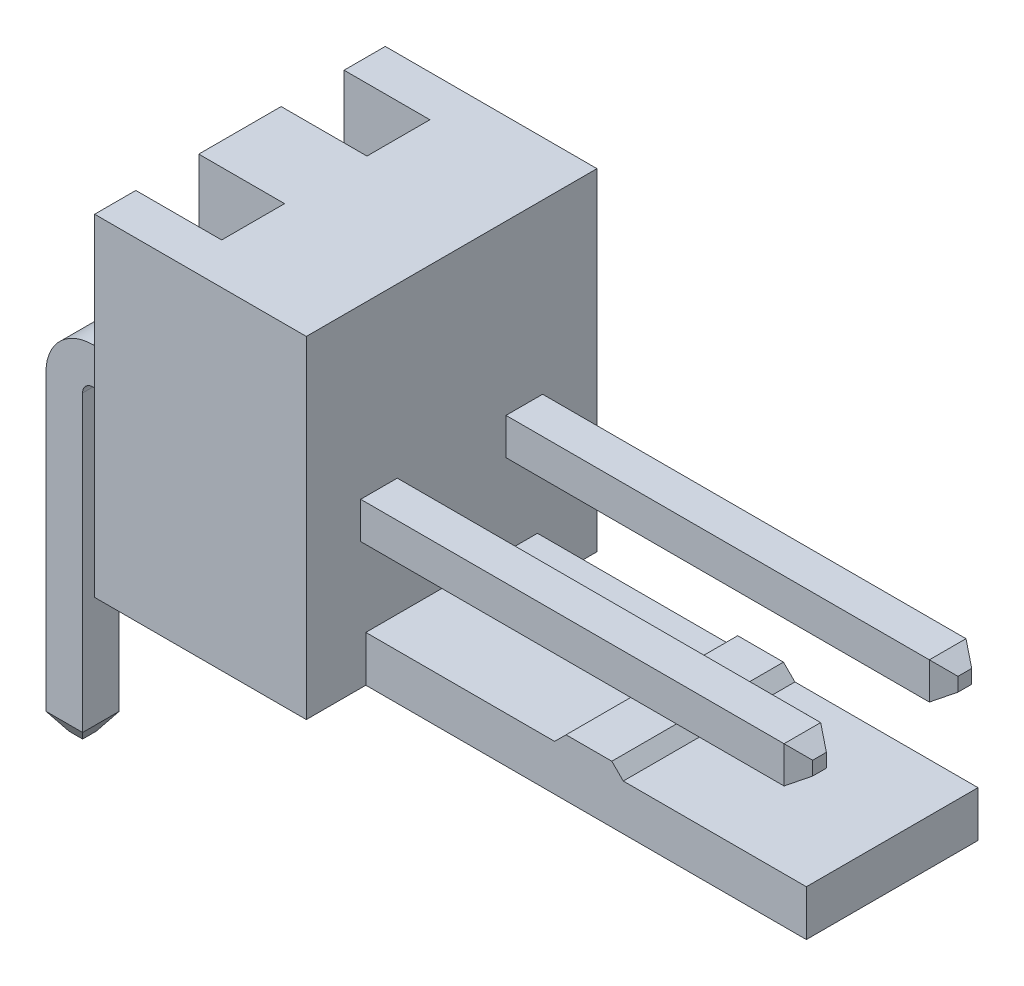
SolidWorks part; units mm, degrees
ref_plane "Спереди" through (0, 0, 0) normal (0, 0, 1) x (1, 0, 0)
ref_plane "Сверху" through (0, 0, 0) normal (0, 1, 0) x (1, 0, 0)
ref_plane "Справа" through (0, 0, 0) normal (1, 0, 0) x (0, 0, -1)
sketch "Эскиз1" plane through (0, 0, 0) normal (1, 0, 0) x (0, 0, -1)
  line L1 (-2.54, 5.8) -> (2.54, 5.8)
  line L2 (-2.54, 5.8) -> (-2.54, 0)
  line L3 (-2.54, 0) -> (2.54, 0)
  line L4 (2.54, 5.8) -> (2.54, 0)
  line L5 (-2.54, 5.8) -> (2.54, 0) construction
  line L6 (-2.54, 0) -> (2.54, 5.8) construction
  point P0 (0, 2.9)
  dimension "D1" = 5.8
  dimension "D2" = 5.08
extrude "Бобышка-Вытянуть1" add sketch "Эскиз1" along normal blind 3.7
sketch "Эскиз5" plane through (0, 5.8, 0) normal (0, 1, 0) x (1, 0, 0)
  line L0 (0, 0) -> (3.7, 0) construction
  line L2 (0, 2.54) -> (0, -2.54) construction
  line L3 (0, -0.72) -> (1.5, -0.72)
  line L4 (0, -0.72) -> (0, -1.82)
  line L5 (0, -1.82) -> (1.5, -1.82)
  line L6 (3.7, 2.54) -> (3.7, -2.54) construction
  line L7 (1.5, -0.72) -> (1.5, -1.82)
  line L8 (0, -0.72) -> (1.5, -1.82) construction
  line L9 (0, -1.82) -> (1.5, -0.72) construction
  point P1 (0.75, -1.27)
  dimension "D1" = 2.54
  dimension "D2" = 1.1
  dimension "D3" = 1.5
extrude "Вырез-Вытянуть1" cut sketch "Эскиз5" against normal up to next
sketch "Эскиз3" plane through (0, 0, 0) normal (0, 0, 1) x (1, 0, 0)
  line L0 (-0.98, 2.54) -> (11.4, 2.54)
  line L1 (-1.48, 2.04) -> (-1.48, -3.4)
  line L2 (3.7, 5.8) -> (0, 5.8) construction
  line L3 (3.7, 0) -> (0, 0) construction
  line L4 (3.7, 5.8) -> (3.7, 0) construction
  line L5 (0, 5.8) -> (0, 0) construction
  arc A0 (-1.48, 2.04) -> (-0.98, 2.54) centre (-0.98, 2.04) cw
  dimension "D5" = 0.5
  dimension "D1" = 3.26
  dimension "D2" = 3.4
  dimension "D3" = 7.7
  dimension "D4" = 1.48
extrude "Вытянуть-Тонкостенный1" add sketch "Эскиз3" along normal mid plane 0.64 from offset 1.27 thin thin type mid plane wall 0.64
chamfer "Фаска1" distance 0.2 distance2 0.3 4 edges at (11.4, 2.22, 1.27) (11.4, 2.54, 1.59) (11.4, 2.86, 1.27) (11.4, 2.54, 0.95)
chamfer "Фаска2" distance 0.2 distance2 0.3 4 edges at (-1.8, -3.4, 1.27) (-1.48, -3.4, 1.59) (-1.16, -3.4, 1.27) (-1.48, -3.4, 0.95)
sketch "Эскиз4" plane through (0, 0, 0) normal (0, 0, 1) x (1, 0, 0)
  line L0 (3.7, 0) -> (3.7, 0.8)
  line L1 (3.7, 5.8) -> (3.7, 0) construction
  line L2 (3.7, 0.8) -> (7, 0.8)
  line L3 (11.4, 0.8) -> (11.4, 0)
  line L4 (11.4, 0) -> (3.7, 0)
  line L5 (7, 0.8) -> (7.2, 1)
  line L6 (7.2, 1) -> (8, 1)
  line L7 (8, 1) -> (8.2, 0.8)
  line L8 (0, 5.8) -> (0, 0) construction
  line L9 (8.2, 0.8) -> (11.4, 0.8)
  dimension "D1" = 0.8
  dimension "D2" = 11.4
  dimension "D3" = 1
  dimension "D4" = 0.8
  dimension "D5" = 3.5
extrude "Бобышка-Вытянуть2" add sketch "Эскиз4" along normal mid plane 3
pattern_linear "Линейный массив2" count 2 spacing 2.54 along (0, 0, -1) of "Вырез-Вытянуть1", "Вытянуть-Тонкостенный1", "Фаска1", "Фаска2"
